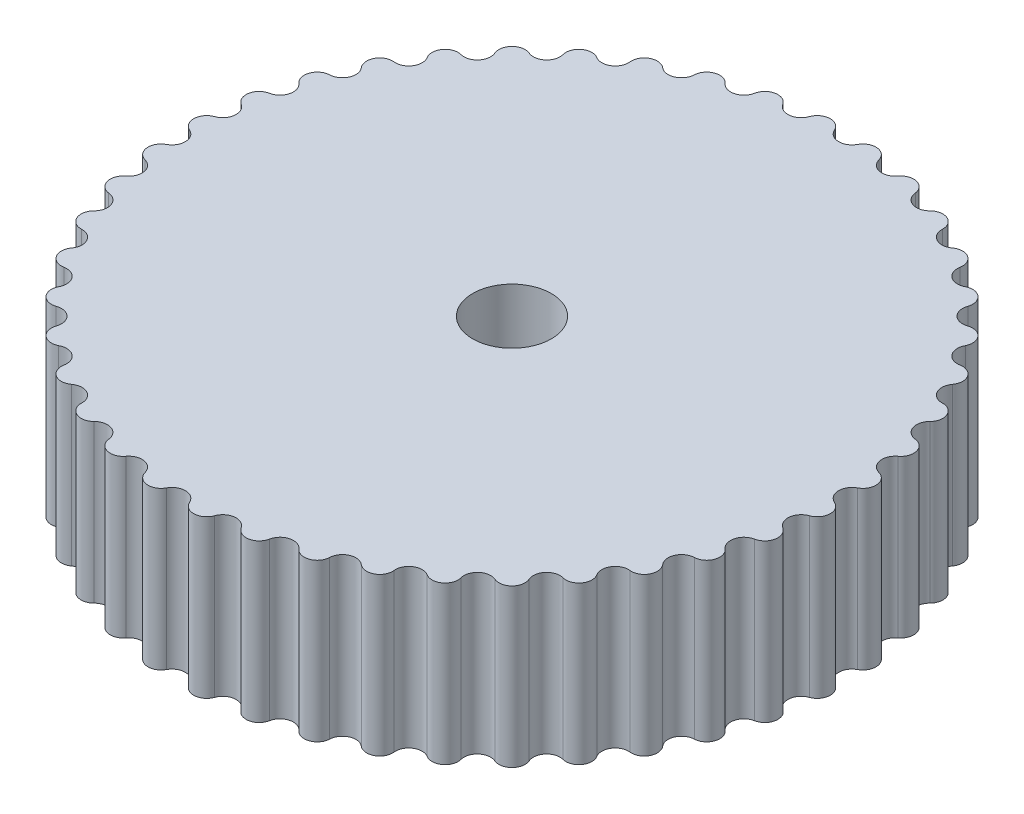
SolidWorks part; units mm, degrees
note: '?' marks a value the reader was unsure of.
ref_plane "Front Plane" through (0, 0, 0) normal (0, 0, 1) x (1, 0, 0)
ref_plane "Top Plane" through (0, 0, 0) normal (0, 1, 0) x (1, 0, 0)
ref_plane "Right Plane" through (0, 0, 0) normal (1, 0, 0) x (0, 0, -1)
sketch "Sketch1" plane through (0, 0, 0) normal (0, 1, 0) x (1, 0, 0)
  line L0 (0, 40) -> (0, 42) construction
  line L1 (2.9892, 39.8882) -> (3.1387, 41.8826) construction
  line L2 (5.9617, 39.5532) -> (6.2598, 41.5309) construction
  line L3 (0, 41) -> (0, 5)
  line L4 (0.7452, 4.9442) -> (6.1107, 40.5421)
  circle A0 centre (0, 0) radius 40 construction
  arc A1 (0, 41) -> (3.0639, 40.8854) centre (1.559, 41.6663) ccw
  arc A2 (6.2598, 41.5309) -> (0, 42) centre (0, 0) ccw construction
  arc A3 (3.0639, 40.8854) -> (6.1107, 40.5421) centre (4.517, 40.0896) cw
  arc A4 (0.7452, 4.9442) -> (0, 5) centre (0, 0) ccw
  point P6 (0, 41)
  point P9 (3.0639, 40.8854)
  dimension "D1" = 80
  dimension "D2" = 2
  dimension "D3" = 10
extrude "Boss-Extrude1" add sketch "Sketch1" along normal blind 20
pattern_circular "CirPattern1" count 42 over 360 about axis through (0, 0, 0) along (0, 1, 0) of "Boss-Extrude1"
ref_axis "Axis1" through (0, 0, 0) along (0, 1, 0)?
sketch "Sketch2" plane through (0, 20, 0) normal (0, 1, 0) x (1, 0, 0)
  line L0 (0, 74.1691) -> (0, -78.0459) construction
  line L1 (19.05, 12.7) -> (26.67, 12.7)
  line L2 (19.05, 12.7) -> (19.05, -12.7)
  line L3 (19.05, -12.7) -> (26.67, -12.7)
  line L4 (26.67, 12.7) -> (26.67, -12.7)
  line L5 (-26.67, 12.7) -> (-26.67, -12.7)
  line L6 (-19.05, -12.7) -> (-26.67, -12.7)
  line L7 (-19.05, 12.7) -> (-19.05, -12.7)
  line L8 (-19.05, 12.7) -> (-26.67, 12.7)
  point P6 (19.05, 0)
  point P12 (-19.05, 0)
  dimension "D1" = 7.62
  dimension "D2" = 25.4
  dimension "D3" = 19.05
